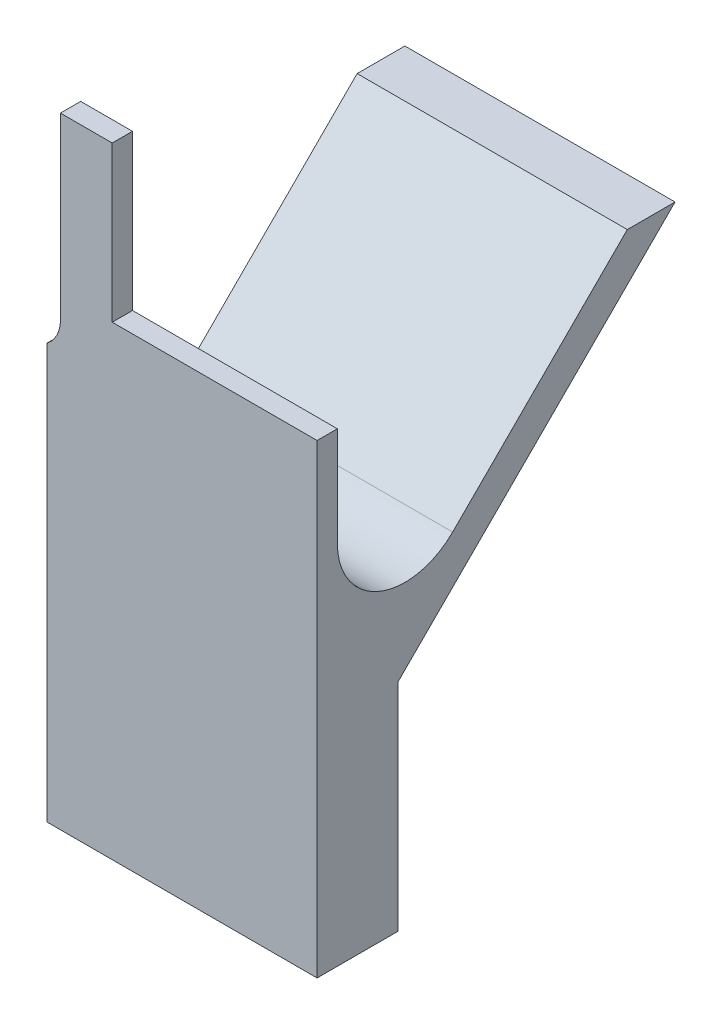
SolidWorks part; units mm, degrees
material "ABS"
ref_plane "Спереди" through (0, 0, 0) normal (0, 0, 1) x (1, 0, 0)
ref_plane "Сверху" through (0, 0, 0) normal (0, 1, 0) x (1, 0, 0)
ref_plane "Справа" through (0, 0, 0) normal (1, 0, 0) x (0, 0, -1)
sketch "Эскиз1" plane through (0, 0, 0) normal (0, 0, 1) x (1, 0, 0)
  line L1 (0, 0) -> (40, 0)
  line L2 (0, 0) -> (0, 32)
  line L3 (0, 32) -> (40, 32)
  line L4 (40, 0) -> (40, 32)
  dimension "D1" = 40
  dimension "D2" = 32
extrude "Бобышка-Вытянуть1" add sketch "Эскиз1" along normal blind 12
sketch "Эскиз2" plane through (0, 0, 12) normal (0, 0, 1) x (1, 0, 0)
  line L0 (40, 32) -> (0, 32) construction
  line L1 (40, 68.92) -> (9.67, 68.92)
  line L2 (40, 68.92) -> (40, 32)
  line L3 (40, 32) -> (9.67, 32)
  line L4 (9.67, 68.92) -> (9.67, 61.4)
  line L6 (0, 61.4) -> (9.67, 61.4)
  line L7 (0, 61.4) -> (0, 32)
  line L8 (0, 32) -> (9.67, 32)
extrude "Бобышка-Вытянуть2" add sketch "Эскиз2" against normal blind 3
fillet "Скругление1" radius 10 1 edges at (20, 32, 9)
sketch "Эскиз3" plane through (0, 0, 0) normal (-1, 0, 0) x (0, 0, 1)
  line L0 (-50, 82) -> (0, 32)
  line L1 (0, 32) -> (0, 0) construction
  line L2 (-44.3431, 83.4142) -> (6.5806, 32.4905)
  line L3 (-50, 82) -> (-44.3431, 83.4142)
  line L4 (-46.4645, 85.5355) -> (3.5355, 35.5355) construction
  line L5 (0, 32) -> (0.9532, 30.3667)
  line L6 (0.9532, 30.3667) -> (6.5806, 32.4905)
  arc A0 (0, 32) -> (9, 41.9499) centre (-1, 41.9499) ccw construction
  dimension "D1" = 5
extrude "Бобышка-Вытянуть3" add sketch "Эскиз3" against normal up to surface (40 mm away)
fillet "Скругление2" radius 10 1 edges at (20, 34.0021, 5.069)
sketch "Эскиз4" plane through (40, 0, 0) normal (1, 0, 0) x (0, 0, -1)
  line L0 (50, 82) -> (13.5873, 82)
  line L1 (13.5873, 82) -> (15.7367, 91.6666)
  line L2 (15.7367, 91.6666) -> (52.4302, 91.6666)
  line L3 (52.4302, 91.6666) -> (50.2808, 82)
sketch "Эскиз5" plane through (40, 0, 0) normal (1, 0, 0) x (0, 0, -1)
  line L0 (50, 82) -> (39.1765, 82)
  line L1 (50, 82) -> (0, 32) construction
  line L2 (39.1765, 82) -> (40.7689, 85.053)
  line L3 (40.7689, 85.053) -> (48.4411, 85.5355)
  line L4 (48.4411, 85.5355) -> (50, 82)
extrude "Вырез-Вытянуть4" cut sketch "Эскиз5" against normal through all
sketch "Эскиз6" plane through (40, 0, 0) normal (1, 0, 0) x (0, 0, -1)
  line L1 (34.9289, 74) -> (42, 74)
  line L2 (42, 74) -> (50, 82)
  line L3 (50, 82) -> (0, 32) construction
  line L4 (42.9289, 82) -> (50, 82) construction
  line L5 (50, 82) -> (42.9289, 82)
  line L6 (42.9289, 82) -> (34.9289, 74)
extrude "Бобышка-Вытянуть4" add sketch "Эскиз6" along normal blind 10
sketch "Эскиз7" plane through (0, 0, 0) normal (-1, 0, 0) x (0, 0, 1)
  line L1 (-42, 74) -> (-34.9289, 74)
  line L4 (-50, 82) -> (0, 32) construction
  line L10 (-42, 74) -> (-50, 82)
  line L11 (-50, 82) -> (-42.9289, 82)
  line L12 (-42.9289, 82) -> (-50, 82) construction
  line L13 (-42.9289, 82) -> (-34.9289, 74)
extrude "Бобышка-Вытянуть5" add sketch "Эскиз7" along normal blind 10
sketch "Эскиз8" plane through (-10, 0, 0) normal (-1, 0, 0) x (0, 0, 1)
  line L0 (-42, 74) -> (-58, 74)
  line L1 (-42, 74) -> (-34.9289, 74) construction
  line L2 (-42, 74) -> (-34.9289, 74) construction
  line L3 (-58, 74) -> (-58, 82)
  line L4 (-58, 82) -> (-50, 82)
  line L5 (-50, 82) -> (-42, 74) construction
  line L6 (-42.9289, 82) -> (-50, 82) construction
  line L7 (-50, 82) -> (-42, 74)
  dimension "D1" = 8
extrude "Бобышка-Вытянуть6" add sketch "Эскиз8" against normal blind 10
sketch "Эскиз9" plane through (50, 0, 0) normal (1, 0, 0) x (0, 0, -1)
  line L0 (42, 74) -> (58, 74)
  line L1 (58, 74) -> (42, 74) construction
  line L2 (42, 74) -> (50, 82) construction
  line L4 (50, 82) -> (42.9289, 82) construction
  line L5 (50, 82) -> (58, 82) construction
  line L6 (50, 82) -> (58, 82)
  line L7 (58, 82) -> (58, 74)
  line L8 (42, 74) -> (50, 82)
extrude "Бобышка-Вытянуть7" add sketch "Эскиз9" against normal blind 10
fillet "Скругление3" radius 3 2 edges at (0, 78, -46) (40, 78, -46)
sketch "Эскиз10" plane through (0, 0, 12) normal (0, 0, -1) x (-1, 0, 0)
  line L0 (-9.67, 91.9) -> (-2, 91.9)
  line L1 (-2, 91.9) -> (-2, 65.4)
  line L3 (0, 61.4) -> (-9.67, 61.4)
  line L4 (-9.67, 61.4) -> (-9.67, 91.9)
  arc A0 (0, 61.4) -> (-2, 65.4) centre (3, 65.4) cw
extrude "Бобышка-Вытянуть8" add sketch "Эскиз10" along normal blind 3
sketch "Эскиз11" plane through (50, 0, 0) normal (1, 0, 0) x (0, 0, -1)
  line L1 (31.9984, 73) -> (61.5924, 73)
  line L2 (31.9984, 73) -> (31.9984, 88.5095)
  line L3 (31.9984, 88.5095) -> (61.5924, 88.5095)
  line L4 (61.5924, 73) -> (61.5924, 88.5095)
extrude "Вырез-Вытянуть5" cut sketch "Эскиз11" against normal through all
